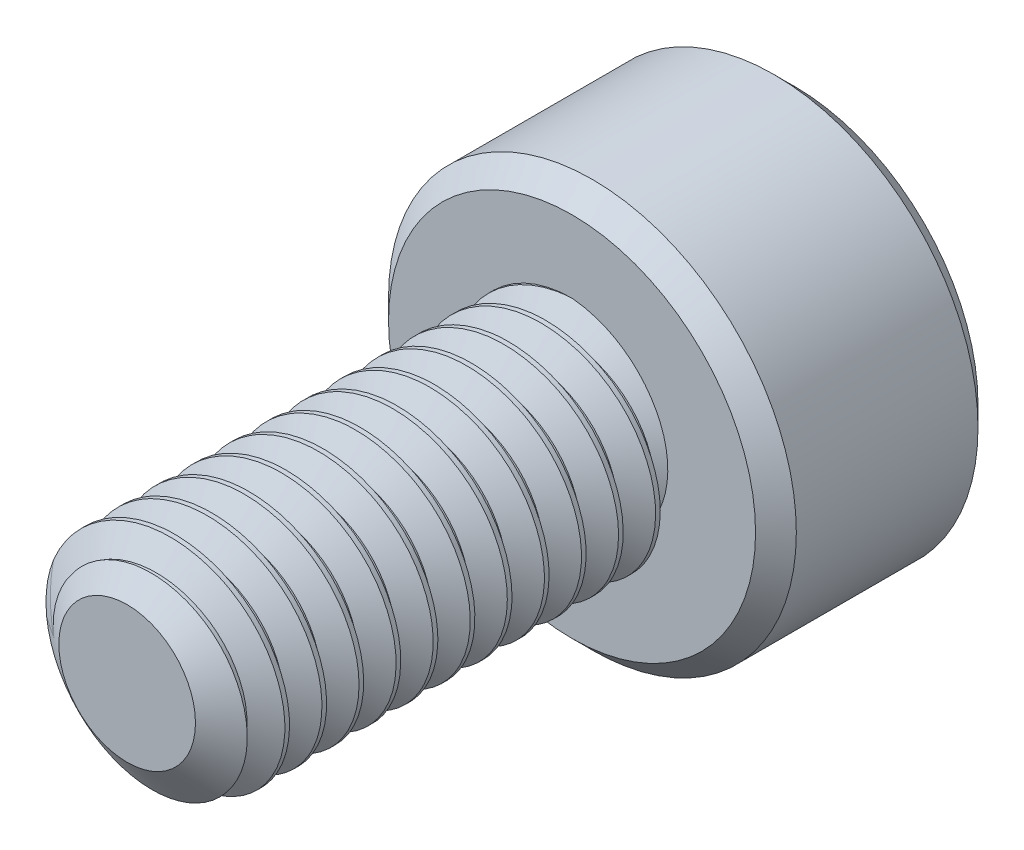
SolidWorks part; units mm, degrees
other "DetailItem1"
ref_plane "Front Plane" through (0, 0, 0) normal (0, 0, 1) x (1, 0, 0)
ref_plane "Top Plane" through (0, 0, 0) normal (0, 1, 0) x (1, 0, 0)
ref_plane "Right Plane" through (0, 0, 0) normal (1, 0, 0) x (0, 0, -1)
sketch "Sketch1" plane through (0, 0, 0) normal (0, 0, 1) x (1, 0, 0)
  circle A0 centre (0, 0) radius 1.5
  dimension "OD" = 3
extrude "Extrude1" add sketch "Sketch1" against normal blind 6
sketch "Sketch2" plane through (0, 0, 0) normal (0, 0, 1) x (1, 0, 0)
  circle A0 centre (0, 0) radius 1.5 construction
  circle A1 centre (0, 0) radius 1.5
curve "Helix/Spiral1" pitch 0.5 height 6.5 radius 1.5 centre (0, 0, 0) axis (0, 0, -1) start towards (0, 1, 0) parameters "pitch"=0.5
sketch "Sketch3" plane through (0, 0, 0) normal (1, 0, 0) x (0, 0, -1)
  line L0 (-0.4375, 1.5) -> (-0.25, 1.1752)
  line L1 (-0.25, 1.1752) -> (-0.1875, 1.1752)
  line L2 (-0.1875, 1.1752) -> (0, 1.5)
  line L3 (-0.4375, 1.5) -> (0, 1.5)
  line L4 (-0.2187, 1.5) -> (-0.2188, 1.1752) construction
  line L5 (-0.3438, 1.3376) -> (-0.0938, 1.3376) construction
  line L6 (0, 1.5) -> (0, -1.5) construction
  dimension "D1" = 0.0625
  dimension "D2" = 0.25
  dimension "D3" = 60
sweep "Cut-Sweep1" cut profiles "Sketch3" path "Helix/Spiral1" align with end faces yes
sketch "Sketch4" plane through (0, 0, 0) normal (1, 0, 0) x (0, 0, -1)
  line L0 (0.4053, 1.5) -> (0, 0.9212)
  line L1 (0, 0.9212) -> (0, 1.5)
  line L2 (0.4053, 1.5) -> (0, 1.5)
  line L3 (-0.4375, 1.5) -> (0, 1.5) construction
  line L4 (0, 0) -> (7.0209, 0) construction
  dimension "D1" = 55
  dimension "D2" = 0.254
revolve "Cut-Revolve1" cut sketch "Sketch4" angle 360 about L4
sketch "Sketch6" plane through (0, 0, -6) normal (0, 0, -1) x (-1, 0, 0)
  circle A0 centre (0, 0) radius 2.75
  dimension "head dia" = 5.5
extrude "Extrude2" add sketch "Sketch6" along normal blind 3
sketch "Sketch7" plane through (0, 0, -9) normal (0, 0, -1) x (-1, 0, 0)
  line L1 (0, 1.4434) -> (-1.25, 0.7217)
  line L2 (-1.25, 0.7217) -> (-1.25, -0.7217)
  line L3 (-1.25, -0.7217) -> (0, -1.4434)
  line L4 (0, -1.4434) -> (1.25, -0.7217)
  line L5 (1.25, -0.7217) -> (1.25, 0.7217)
  line L6 (1.25, 0.7217) -> (0, 1.4434)
  circle A0 centre (0, 0) radius 1.25 construction
  dimension "hex dia" = 2.5
extrude "Cut-Extrude1" cut sketch "Sketch7" against normal blind 1.875
sketch "Sketch8" plane through (0, 0, -9) normal (0, 0, -1) x (-1, 0, 0)
  circle A0 centre (0, 0) radius 1.4434
extrude "Cut-Extrude2" cut sketch "Sketch8" against normal through all draft 45
chamfer "Chamfer1" distance 0.275 angle 45 2 edges at (-2.75, 0, -9) (-2.75, 0, -6)
sketch "Sketch10" plane through (0, 0, -6) normal (0, 0, 1) x (1, 0, 0)
  circle A1 centre (0, 0) radius 1.5
  circle A2 centre (0, 0) radius 1.5
  dimension "D1" = 0
ref_plane "Plane1" through (0, 0, 0) normal (0, 0, 1) x (1, 0, 0)
extrude "partial thread" [suppressed] add sketch "Sketch10" along normal up to surface (4 mm away) separate body up to plane "Plane1"
chamfer "Chamfer2" [suppressed] distance 0.06 angle 45
combine bodies "Combine1" [suppressed] operation type add bodies to combine 107 108
sketch "Sketch9" plane through (0, 0, 0) normal (1, 0, 0) x (0, 0, -1)
  line L0 (0, 1.5) -> (0, -1.5) construction
  line L1 (1.25, 1.5) -> (1.25, -1.5) construction
  dimension "D1" = 1.25
equation "\"D3@Helix/Spiral1\" = \"screw length@Extrude1\"+\"pitch@Helix/Spiral1\""
equation "\"D1@Sketch3\" = \"pitch@Helix/Spiral1\"*.125"
equation "\"D2@Sketch3\" = \"pitch@Helix/Spiral1\"*.5"
equation "\"D1@Cut-Extrude1\" = \"hex dia@Sketch7\"*.75"
equation "\"D1@Chamfer1\" = \"head dia@Sketch6\"*.05"
equation "\"D1@Sketch9\" = \"pitch@Helix/Spiral1\"*2.5"
equation "\"D1@Chamfer2\"=\"OD@Sketch1\"*.02"
